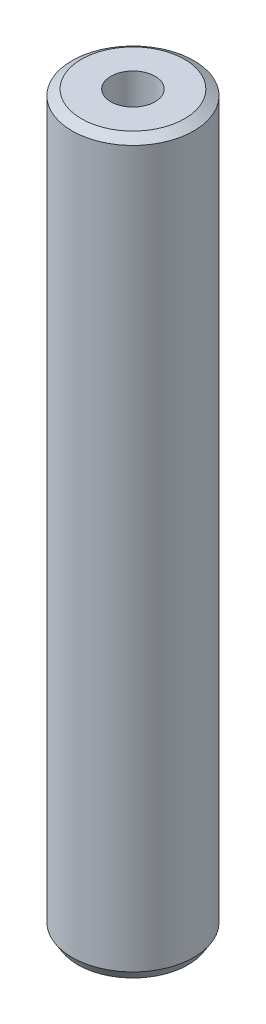
SolidWorks part; units mm, degrees
ref_plane "Front Plane" through (0, 0, 0) normal (0, 0, 1) x (1, 0, 0)
ref_plane "Top Plane" through (0, 0, 0) normal (0, 1, 0) x (1, 0, 0)
ref_plane "Right Plane" through (0, 0, 0) normal (1, 0, 0) x (0, 0, -1)
sketch "Sketch1" plane through (0, 0, 0) normal (0, 1, 0) x (1, 0, 0)
  circle A0 centre (0, 0) radius 50
  dimension "SHAFT_OD" = 100
extrude "Boss-Extrude1" add sketch "Sketch1" along normal blind 600
sketch "Sketch2" plane through (0, 0, 0) normal (0, 1, 0) x (1, 0, 0)
  circle A0 centre (0, 0) radius 18.1611
  dimension "BORE_D" = 36.3222
extrude "Cut-Extrude1" cut sketch "Sketch2" along normal through all
chamfer "Chamfer1" distance 4.7722 angle 58.113 2 edges at (0, 600, 50) (0, 0, 50) first distance on face at (0, 600, 50) first distance on face at (0, 0, 18.1611)
